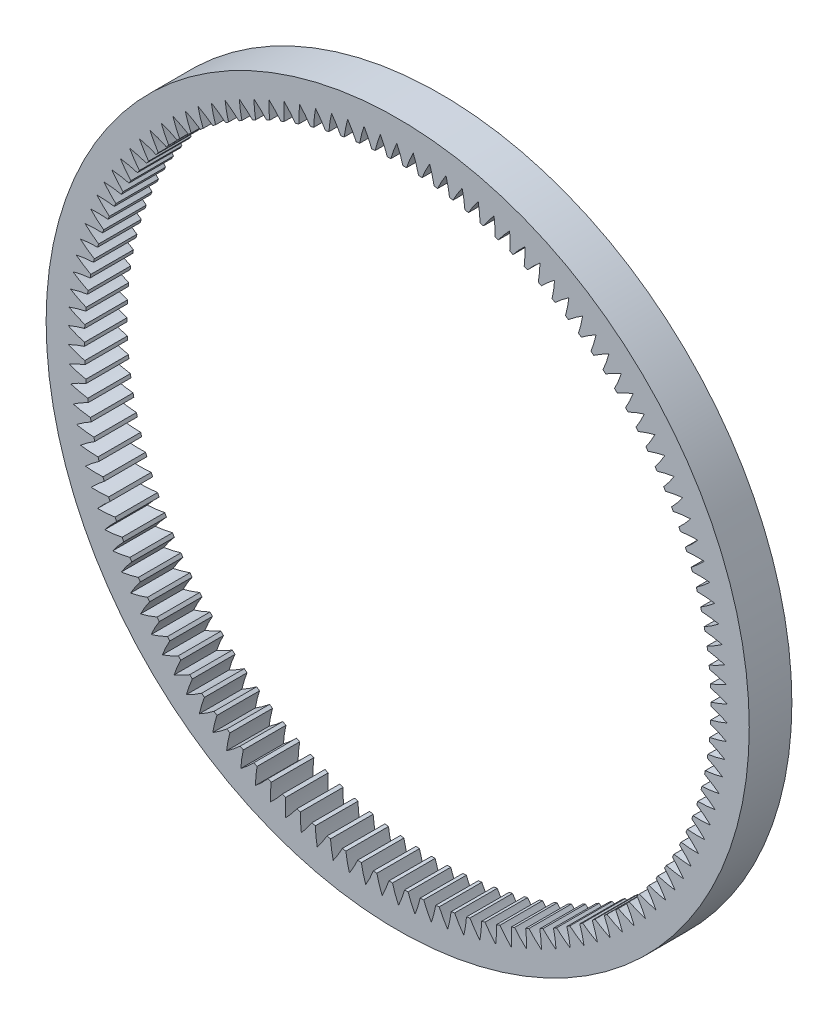
SolidWorks part; units mm, degrees
ref_plane "Front Plane" through (0, 0, 0) normal (0, 0, 1) x (1, 0, 0)
ref_plane "Top Plane" through (0, 0, 0) normal (0, 1, 0) x (1, 0, 0)
ref_plane "Right Plane" through (0, 0, 0) normal (1, 0, 0) x (0, 0, -1)
sketch "Sketch1" plane through (0, 0, 0) normal (0, 0, 1) x (1, 0, 0)
  line L0 (0, 0) -> (152.3804, 0.3964) construction
  line L1 (0, 0) -> (7.4762, 0.2059) construction
  line L2 (0, 0) -> (152.3804, 0.3964) construction
  line L3 (0, 0) -> (152.3637, 2.296) construction
  line L4 (0, 0) -> (152.1713, 7.9915) construction
  line L5 (147.0233, 0.3825) -> (164.9994, 0.4293)
  line L6 (7.4762, 0.2059) -> (164.9375, 4.5427)
  circle A0 centre (0, 0) radius 150 construction
  circle A1 centre (0, 0) radius 147.0238 construction
  circle A2 centre (0, 0) radius 140.9539 construction
  circle A3 centre (0, 0) radius 152.381 construction
  arc A4 (146.9949, 2.9152) -> (147.0233, 0.3825) centre (0, 0) cw
  arc A5 (164.9375, 4.5427) -> (164.9994, 0.4293) centre (0, 0) cw
  spline S0 degree 4 poles (140.9539, 0) (141.047, 0.0021) (141.233, 0.0096) (141.6043, 0.0381) (142.1413, 0.0988) (142.7502, 0.1881) (143.5952, 0.3382) (144.7155, 0.5763) (146.1211, 0.9353) (148.5424, 1.6703) (151.8418, 2.9113) (156.3125, 4.9787) (161.7974, 8.1307) (167.5079, 12.0923) (173.2947, 16.8502) (178.7179, 22.0165) (183.7842, 27.5321) (188.7334, 33.6368) (194.3854, 41.5588) (200.3945, 51.493) (206.3549, 63.5923) (211.0515, 75.8366) (214.322, 86.5835) (217.006, 97.4872) (218.7638, 106.6813) (220.0572, 115.9516) (220.9004, 125.2707) (221.3104, 132.7451) (221.4993, 142.1002) (221.2188, 153.3279) (220.176, 166.3924) (218.4445, 178.4384) (216.692, 187.63) (215.3753, 193.5675) (214.7345, 196.2984) (214.1768, 198.5735) (213.7205, 200.3797) (213.2864, 202.0439) (212.8968, 203.5028) (212.5227, 204.8688) (212.2249, 205.9419) (211.8226, 207.3585) (211.531, 208.3682) (211.0466, 210.0184) (210.6618, 211.2901) (210.1884, 212.8378) (209.7547, 214.2166) (209.2845, 215.691) (208.8222, 217.1072) (208.224, 218.9088) (207.4957, 221.0461) (206.6187, 223.5443) (205.7164, 226.0241) (204.9217, 228.1477) (204.3824, 229.5564) (204.1096, 230.2614) (203.9728, 230.6129) knots 0 0 0 0 0 0.001401 0.002802 0.005604 0.008133 0.010661 0.015718 0.022839 0.02996 0.048734 0.068727 0.096889 0.125051 0.153212 0.181374 0.209535 0.237696 0.271429 0.327752 0.384075 0.440398 0.46856 0.496721 0.553044 0.581206 0.609367 0.637529 0.66569 0.722013 0.778336 0.834659 0.84874 0.86282 0.869861 0.876901 0.883942 0.890982 0.895509 0.900036 0.904564 0.909091 0.914773 0.920455 0.926136 0.931818 0.9375 0.943182 0.948864 0.954545 0.965909 0.977273 0.988636 0.994318 1 1 1 1 1 construction
  spline S1 degree 4 poles (140.9539, 0) (141.047, 0.0021) (141.233, 0.0096) (141.6043, 0.0381) (142.1413, 0.0988) (142.7502, 0.1881) (143.5952, 0.3382) (144.7155, 0.5763) (146.1211, 0.9353) (148.5424, 1.6703) (151.8418, 2.9113) (156.3125, 4.9787) (161.7974, 8.1307) (167.5079, 12.0923) (173.2947, 16.8502) (178.7179, 22.0165) (183.7842, 27.5321) (188.7334, 33.6368) (194.3854, 41.5588) (200.3945, 51.493) (206.3549, 63.5923) (211.0515, 75.8366) (214.322, 86.5835) (217.006, 97.4872) (218.7638, 106.6813) (220.0572, 115.9516) (220.9004, 125.2707) (221.3104, 132.7451) (221.4993, 142.1002) (221.2188, 153.3279) (220.176, 166.3924) (218.4445, 178.4384) (216.692, 187.63) (215.3753, 193.5675) (214.7345, 196.2984) (214.1768, 198.5735) (213.7205, 200.3797) (213.2864, 202.0439) (212.8968, 203.5028) (212.5227, 204.8688) (212.2249, 205.9419) (211.9413, 206.9407) (211.7889, 207.4725) (211.7131, 207.7353) knots 0 0 0 0 0 0.001401 0.002802 0.005604 0.008133 0.010661 0.015718 0.022839 0.02996 0.048734 0.068727 0.096889 0.125051 0.153212 0.181374 0.209535 0.237696 0.271429 0.327752 0.384075 0.440398 0.46856 0.496721 0.553044 0.581206 0.609367 0.637529 0.66569 0.722013 0.778336 0.834659 0.84874 0.86282 0.869861 0.876901 0.883942 0.890982 0.895509 0.900036 0.904564 0.909091 0.909091 0.909091 0.909091 0.909091
  point P6 (147.0071, 2.2153)
  point P14 (147.0188, 1.2154)
  point P19 (146.9949, 2.9152)
  dimension "pitchRadius" = 150
  dimension "addendumRadius" = 152.381
  dimension "dedendumRadius" = 147.0238
  dimension "baseRadius" = 140.9539
  dimension "D1" = 1.429
  dimension "D2" = 0.714
  dimension "toothArc" = 2.857
  dimension "backlash" = 1
  dimension "D3" = 165
extrude "Boss-Extrude1" add sketch "Sketch1" along normal blind 20 contours S1 region at (157.4775, 2.1954, 0)
mirror "Mirror1" about plane through (0, 0, 20) normal (-0.0275, 0.9996, 0) of "Boss-Extrude1"
pattern_circular "CirPattern2" count 126 over 360 about axis through (0, 0, 20) along (0, 0, -1) of "Boss-Extrude1", "Mirror1"
equation "\"D2@Sketch1\"=\"toothArc@Sketch1\"/4"
equation "\"pitchRadius\"= 15"
equation "\"nTeeth\"= 126"
equation "\"pressureAngle\"= 20"
equation "\"baseRadius\"= \"pitchRadius\" * cos ( \"pressureAngle\" )"
equation "\"diametralPitch\"= \"nTeeth\" / ( 2 * \"pitchRadius\" )'note units: cm^-1"
equation "\"dedendum\"= 1.25 / \"diametralPitch\"'for full depth, 20 deg pressure angle"
equation "\"addendum\"= 1 / \"diametralPitch\""
equation "\"pitchRadius@Sketch1\"= \"pitchRadius\""
equation "\"addendumRadius@Sketch1\"= \"pitchRadius\" + \"addendum\""
equation "\"dedendumRadius@Sketch1\"= \"pitchRadius\" - \"dedendum\""
equation "\"baseRadius@Sketch1\"= \"baseRadius\""
equation "\"D2@CirPattern2\"= \"nTeeth\""
equation "\"D1@CirPattern2\"=\"nTeeth\""
equation "\"toothArc@Sketch1\"=360/\"nTeeth\""
equation "\"D1@Sketch1\"=\"toothArc@Sketch1\"/2"
